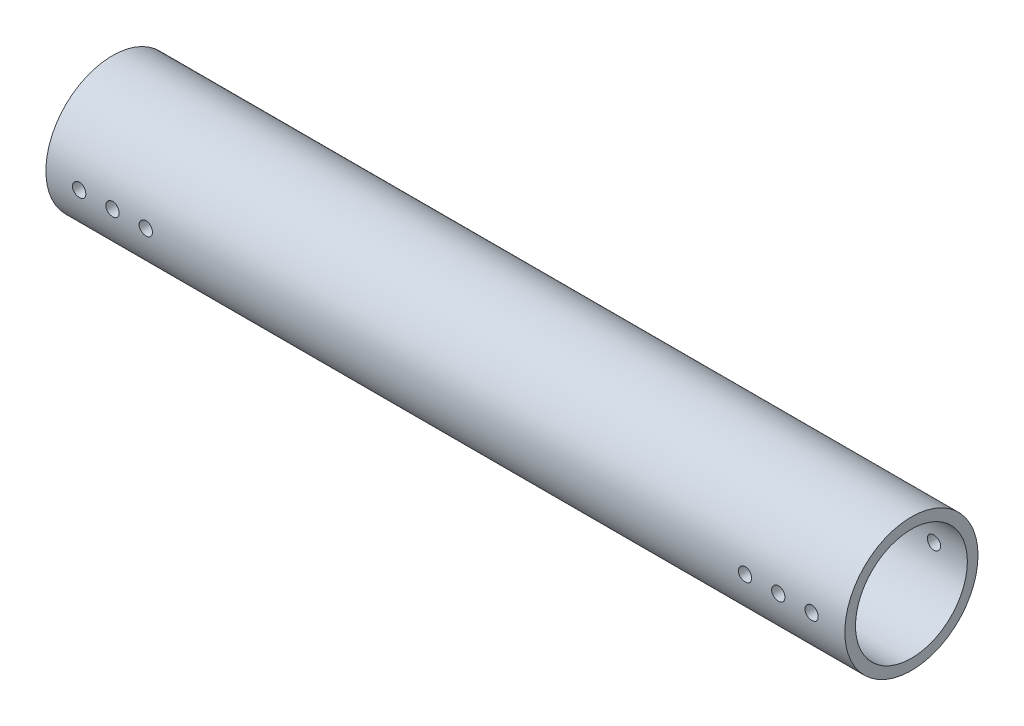
SolidWorks part; units mm, degrees
material "Zoltek Panex 33"
ref_plane "Спереди" through (0, 0, 0) normal (0, 0, 1) x (1, 0, 0)
ref_plane "Сверху" through (0, 0, 0) normal (0, 1, 0) x (1, 0, 0)
ref_plane "Справа" through (0, 0, 0) normal (1, 0, 0) x (0, 0, -1)
other "Configuration Table"
sketch "Эскиз2" plane through (0, 0, 0) normal (1, 0, 0) x (0, 0, -1)
  circle A0 centre (0, 0) radius 25
  circle A1 centre (0, 0) radius 21
  dimension "D1" = 50
  dimension "D2" = 42
extrude "Бобышка-Вытянуть2" add sketch "Эскиз2" along normal blind 300
ref_plane "Плоскость1" through (0, 0, 25) normal (0, 0, 1) x (1, 0, 0)
sketch "Эскиз4" plane through (0, 0, 25) normal (0, 0, 1) x (1, 0, 0)
  line L0 (0, -25) -> (300, -25) construction
  line L1 (300, -25) -> (300, 25) construction
  circle A0 centre (12.5, 0) radius 2.5
  circle A1 centre (287.5, 0) radius 2.5
  circle A2 centre (25, 0) radius 2.5
  circle A3 centre (37.5, 0) radius 2.5
  circle A4 centre (275, 0) radius 2.5
  circle A5 centre (262.5, 0) radius 2.5
  dimension "D1" = 5
  dimension "D4" = 5
  dimension "D6" = 5
  dimension "D8" = 5
  dimension "D10" = 5
  dimension "D11" = 5
  dimension "D2" = 12.5
  dimension "D3" = 25
  dimension "D5" = 12.5
  dimension "D7" = 12.5
  dimension "D9" = 12.5
  dimension "15" = 12.5
  dimension "D12" = 12.5
extrude "Вырез-Вытянуть2" cut sketch "Эскиз4" against normal through all and the other way blind 10 contours A0 | A1 | A2 | A3 | A5 | A4
equation "\"Diameter\"= 50мм"
equation "\"D1@Эскиз2\"= \"Diameter\""
equation "\"Length\"= 300мм"
equation "\"Thickness\"= 4мм"
equation "\"D1@Бобышка-Вытянуть2\"= \"Length\""
equation "\"D2@Эскиз2\" = \"Diameter\" - \"Thickness\" * 2"
equation "\"D4@Эскиз4\"=\"D1@Эскиз4\""
equation "\"D5@Эскиз4\"=\"D2@Эскиз4\""
equation "\"D3@Эскиз4\"=\"Diameter\"/2"
equation "\"D6@Эскиз4\"=\"D1@Эскиз4\""
equation "\"D8@Эскиз4\"=\"D6@Эскиз4\""
equation "\"D10@Эскиз4\"=\"D4@Эскиз4\""
equation "\"D11@Эскиз4\"=\"D4@Эскиз4\""
equation "\"D9@Эскиз4\"=\"D7@Эскиз4\""
